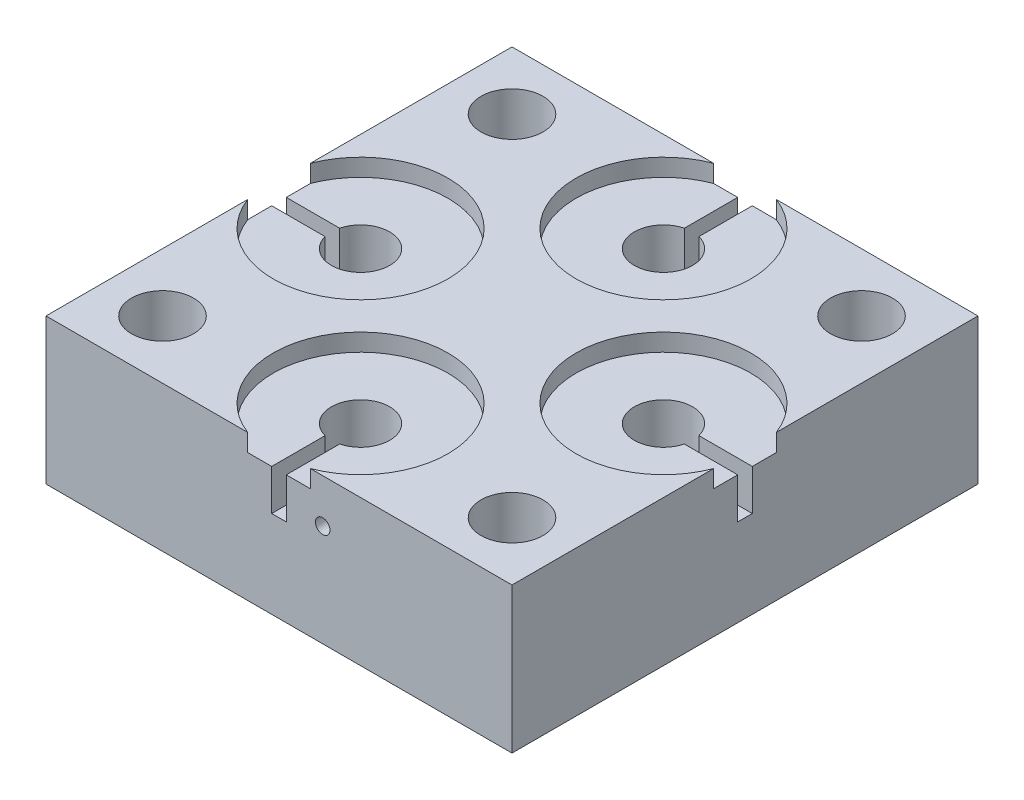
SolidWorks part; units mm, degrees
ref_plane "Front Plane" through (0, 0, 0) normal (0, 0, 1) x (1, 0, 0)
ref_plane "Top Plane" through (0, 0, 0) normal (0, 1, 0) x (1, 0, 0)
ref_plane "Right Plane" through (0, 0, 0) normal (1, 0, 0) x (0, 0, -1)
sketch "Sketch1" plane through (0, 0, 0) normal (0, 1, 0) x (1, 0, 0)
  line L1 (-25.4, 25.4) -> (25.4, 25.4)
  line L2 (-25.4, 25.4) -> (-25.4, -25.4)
  line L3 (-25.4, -25.4) -> (25.4, -25.4)
  line L4 (25.4, 25.4) -> (25.4, -25.4)
  dimension "D1" = 50.8
  dimension "D2" = 50.8
  dimension "D3" = 25.4
  dimension "D4" = 25.4
extrude "Boss-Extrude1" add sketch "Sketch1" along normal blind 15.875
hole_wizard "1/4 Clearance Hole1" positions "Sketch5" profile "Sketch4" hole size "1/4" standard "ANSI Inch" end condition through all
sketch "Sketch5" plane through (0, 15.875, 0) normal (0, 1, 0) x (1, 0, 0)
  point P0 (-19.05, -19.05)
  point P2 (-19.05, 19.05)
  point P4 (19.05, 19.05)
  point P6 (19.05, -19.05)
sketch "Sketch4" plane through (-19.05, 15.875, 19.05) normal (1, 0, 0) x (0, 0, 1)
  line L0 (0, 0) -> (0, 15.875)
  line L1 (0, 15.875) -> (3.3782, 15.875)
  line L2 (3.3782, 15.875) -> (3.3782, 0)
  line L5 (3.3782, 0) -> (0, 0)
  line L11 (0, -6.35) -> (0, 107.95) construction
  dimension "Thru Hole Dia." = 6.7564
  dimension "Thru Hole Depth" = 15.875
sketch "Sketch7" plane through (0, 15.875, 0) normal (0, 1, 0) x (1, 0, 0)
  line L0 (25.4, -25.4) -> (25.4, 25.4) construction
  line L1 (25.4, 25.4) -> (-25.4, 25.4) construction
  circle A0 centre (-16.51, 0) radius 3.175
  circle A1 centre (0, 16.51) radius 3.175
  circle A2 centre (16.51, 0) radius 3.175
  circle A3 centre (0, -16.51) radius 3.175
  circle A4 centre (19.05, -19.05) radius 3.3782 construction
  dimension "D2" = 6.35
  dimension "D1" = 16.51
  dimension "D3" = 16.51
  dimension "D4" = 16.51
  dimension "D5" = 16.51
  dimension "D6" = 25.4
  dimension "D7" = 25.4
extrude "Cut-Extrude2" cut sketch "Sketch7" against normal blind 9.525
hole_wizard "#6 Clearance Hole1" positions "Sketch14" profile "Sketch13" hole size "#6" standard "ANSI Inch" end condition through all
sketch "Sketch14" plane through (0, 6.35, 0) normal (0, 1, 0) x (1, 0, 0)
  point P0 (-16.51, 0)
  point P2 (0, 16.51)
  point P5 (16.51, 0)
  point P8 (0, -16.51)
sketch "Sketch13" plane through (-16.51, 6.35, 0) normal (1, 0, 0) x (0, 0, 1)
  line L0 (0, 0) -> (0, 6.35)
  line L1 (0, 6.35) -> (1.8986, 6.35)
  line L2 (1.8986, 6.35) -> (1.8986, 0)
  line L5 (1.8986, 0) -> (0, 0)
  line L11 (0, -6.35) -> (0, 107.95) construction
  dimension "Thru Hole Dia." = 3.7973
  dimension "Thru Hole Depth" = 6.35
sketch "Sketch15" plane through (0, 0, 0) normal (0, -1, 0) x (1, 0, 0)
  circle A0 centre (0, 16.51) radius 6.35
  circle A1 centre (16.51, 0) radius 6.35
  circle A2 centre (0, -16.51) radius 6.35
  circle A3 centre (-16.51, 0) radius 6.35
  dimension "D1" = 12.7
extrude "Cut-Extrude5" cut sketch "Sketch15" against normal blind 3.175
sketch "Sketch16" plane through (0, 15.875, 0) normal (0, 1, 0) x (1, 0, 0)
  circle A0 centre (0, 0) radius 12.7
sketch "Sketch17" plane through (0, 0, 25.4) normal (0, 0, 1) x (1, 0, 0)
  circle A0 centre (4.7625, 11.1125) radius 0.7938
extrude "Cut-Extrude7" cut sketch "Sketch17" against normal blind 19.05
sketch "Sketch19" plane through (0, 0, -25.4) normal (0, 0, -1) x (-1, 0, 0)
  circle A0 centre (4.7625, 11.1125) radius 0.7937
  circle A1 centre (-4.7625, 11.1125) radius 0.7938 construction
extrude "Cut-Extrude8" cut sketch "Sketch19" against normal blind 19.05
sketch "Sketch20" plane through (0, 15.875, 0) normal (0, 1, 0) x (1, 0, 0)
  line L0 (25.4, 25.4) -> (-25.4, 25.4) construction
  line L1 (-0.7938, 25.4) -> (0.7937, 25.4)
  line L2 (-0.7938, 25.4) -> (-0.7938, 16.4806)
  line L3 (-0.7938, 16.4806) -> (0.7937, 16.4806)
  line L4 (0.7937, 25.4) -> (0.7937, 16.4806)
  line L5 (-25.4, 25.4) -> (-25.4, -25.4) construction
  line L6 (-25.4, 0.7937) -> (-16.7909, 0.7937)
  line L7 (-25.4, 0.7937) -> (-25.4, -0.7937)
  line L8 (-25.4, -0.7937) -> (-16.7909, -0.7937)
  line L9 (-16.7909, 0.7937) -> (-16.7909, -0.7937)
  line L10 (25.4, -25.4) -> (25.4, 25.4) construction
  line L11 (25.4, 0.7938) -> (16.3772, 0.7938)
  line L12 (25.4, 0.7938) -> (25.4, -0.7937)
  line L13 (25.4, -0.7937) -> (16.3772, -0.7937)
  line L14 (16.3772, 0.7938) -> (16.3772, -0.7937)
  line L15 (-25.4, -25.4) -> (25.4, -25.4) construction
  line L16 (-0.7937, -25.4) -> (0.7937, -25.4)
  line L17 (-0.7937, -25.4) -> (-0.7937, -17.0323)
  line L18 (-0.7937, -17.0323) -> (0.7937, -17.0323)
  line L19 (0.7937, -25.4) -> (0.7937, -17.0323)
  dimension "D1" = 1.5875
  dimension "D2" = 0.7937
  dimension "D3" = 0.7937
  dimension "D4" = 1.5875
  dimension "D5" = 0.7937
  dimension "D6" = 1.5875
  dimension "D7" = 0.7937
  dimension "D8" = 1.5875
extrude "Cut-Extrude9" cut sketch "Sketch20" against normal blind 6.35
sketch "Sketch21" plane through (0, 15.875, 0) normal (0, 1, 0) x (1, 0, 0)
  circle A0 centre (-16.51, 0) radius 9.525
  circle A1 centre (16.51, 0) radius 9.525
  circle A2 centre (0, 16.51) radius 9.525
  circle A3 centre (0, -16.51) radius 9.525
  dimension "D1" = 19.05
extrude "Cut-Extrude10" cut sketch "Sketch21" against normal blind 1.905
